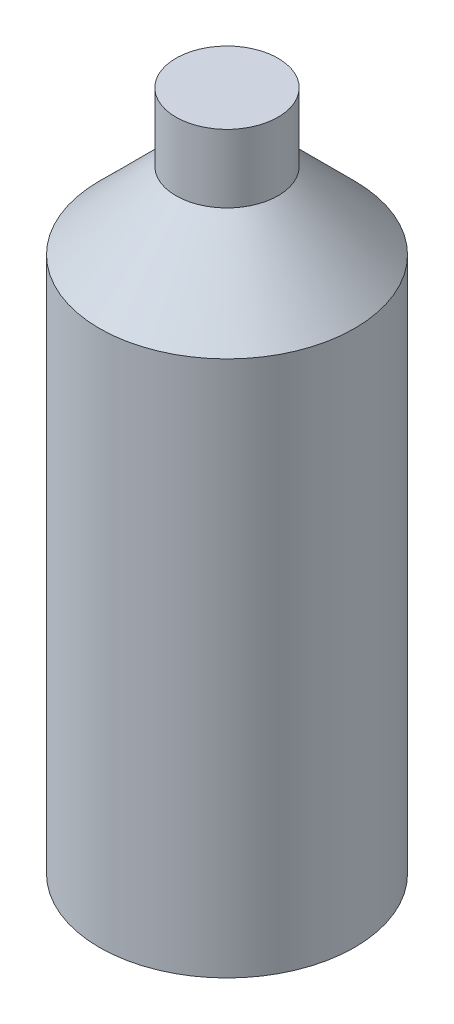
SolidWorks part; units mm, degrees
ref_plane "Face" through (0, 0, 0) normal (0, 0, 1) x (1, 0, 0)
ref_plane "Dessus" through (0, 0, 0) normal (0, 1, 0) x (1, 0, 0)
ref_plane "Droite" through (0, 0, 0) normal (1, 0, 0) x (0, 0, -1)
sketch "Esquisse1" plane through (0, 0, 0) normal (0, 1, 0) x (1, 0, 0)
  circle A0 centre (0, 0) radius 37.5
  dimension "D1" = 75
extrude "Extrusion1" add sketch "Esquisse1" along normal blind 200
sketch "Esquisse2" plane through (0, 200, 0) normal (0, 1, 0) x (1, 0, 0)
  circle A0 centre (0, 0) radius 15
  dimension "D1" = 30
extrude "Extrusion2" cut sketch "Esquisse2" against normal blind 20 flip side to cut
chamfer "Chanfrein1" distance 22.5 angle 45 1 edges at (0, 180, 37.5)
